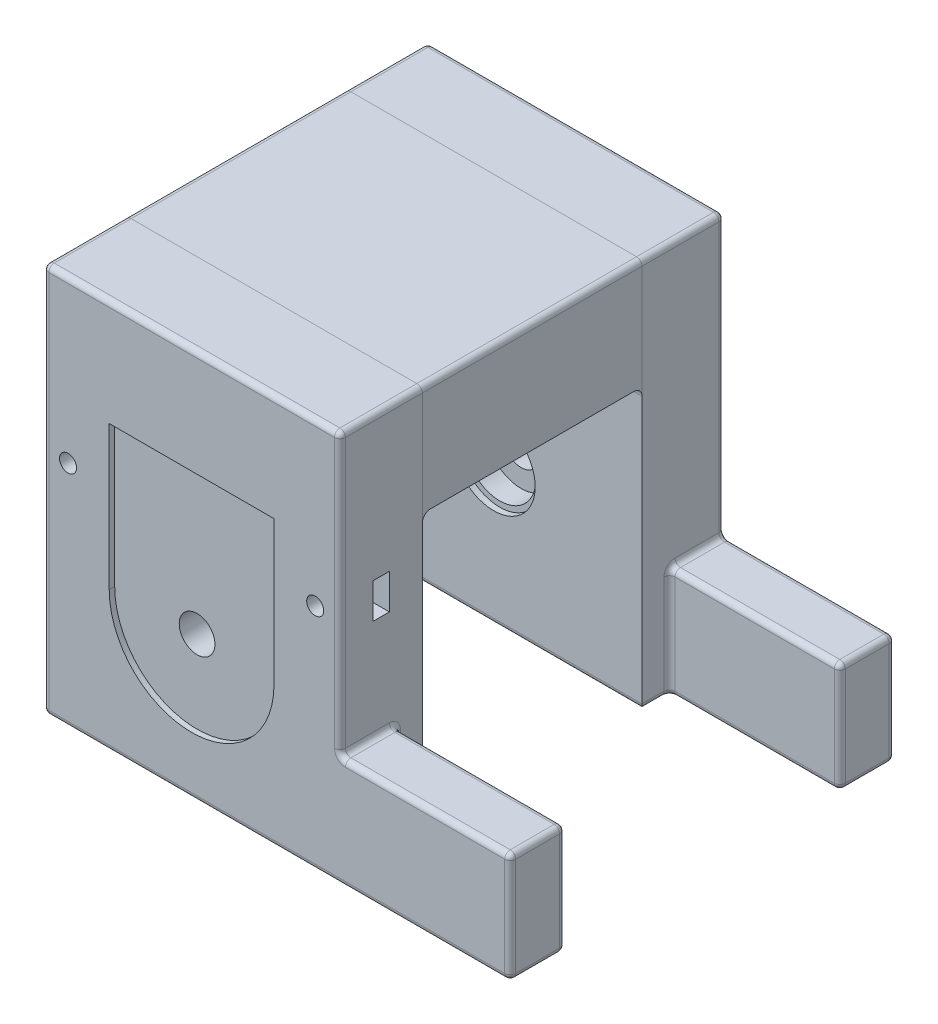
SolidWorks part; units mm, degrees
note: The reader was unsure of these and kept them because the rebuilt part matched: shared geometry of "Esquisse6<4>", "Esquisse6<5>".
ref_plane "Plan de face" through (0, 0, 0) normal (0, 0, 1) x (1, 0, 0)
ref_plane "Plan de dessus" through (0, 0, 0) normal (0, 1, 0) x (1, 0, 0)
ref_plane "Plan de droite" through (0, 0, 0) normal (1, 0, 0) x (0, 0, -1)
sketch "Esquisse1" plane through (0, 0, 0) normal (0, 0, 1) x (1, 0, 0)
  line L0 (0, 15.5) -> (0, -15.5)
  line L2 (0, -15.5) -> (31, -15.5)
  line L4 (0, 35.5) -> (-54, 35.5)
  line L5 (0, 0) -> (5.3833, 0) construction
  line L6 (31, -15.5) -> (31, -35.5)
  line L7 (31, -35.5) -> (-54, -35.5)
  line L8 (-54, 35.5) -> (-54, -35.5)
  line L9 (0, 15.5) -> (0, 35.5)
  point P4 (0, 0)
  dimension "D2" = 54
  dimension "D3" = 20
  dimension "D5" = 71
  dimension "D6" = 5.3833
  dimension "D1" = 31
extrude "Boss.-Extru.1" add sketch "Esquisse1" along normal blind 10
sketch "Esquisse2" plane through (0, 0, 10) normal (0, 0, 1) x (1, 0, 0)
  line L27 (0, 35.5) -> (0, -35.5)
  line L29 (-54, -35.5) -> (31, -35.5) construction
  line L30 (0, 35.5) -> (-54, 35.5)
  line L31 (-54, 35.5) -> (-54, -35.5)
  line L32 (-54, -35.5) -> (0, -35.5)
  point P3 (0, 0)
  point P12 (0, 0)
  point P17 (0, 0)
extrude "Boss.-Extru.2" add sketch "Esquisse2" along normal blind 50
ref_plane "Plan1" through (0, 0, 35) normal (0, 0, 1) x (1, 0, 0)
mirror "Symétrie2" about plane through (0, 0, 35) normal (0, 0, 1) of "Boss.-Extru.1"
fillet "Congé2" radius 1 30 edges at (15.5, -15.5, 0) (31, -15.5, 5) (31, -35.5, 5) (-54, -35.5, 35) (-54, 35.5, 35) (0, 35.5, 35) (0, -15.5, 5) (15.5, -35.5, 10) (0, -25.5, 10) (0, -35.5, 35) (0, -25.5, 60) (31, -25.5, 10) (15.5, -15.5, 60) (0, -15.5, 65) (31, -25.5, 60) (31, -15.5, 65) (15.5, -35.5, 60) (31, -35.5, 65) (15.5, -15.5, 70) (0, 10, 70) (-27, 35.5, 70) (-54, 0, 70) (-11.5, -35.5, 70) (31, -25.5, 70) (15.5, -15.5, 10) (31, -25.5, 0) (-11.5, -35.5, 0) (-54, 0, 0) (-27, 35.5, 0) (0, 10, 0)
sketch "Esquisse3" plane through (-54, 0, 0) normal (-1, 0, 0) x (0, 0, 1)
  line L0 (0, 0) -> (35, 0) construction
  line L1 (35, 0) -> (35, 15.5) construction
  line L6 (16.5, 15.5) -> (53.5, 15.5)
  line L7 (15, 14) -> (15, -35.5)
  line L8 (55, 14) -> (55, -35.5)
  line L9 (55, -35.5) -> (15, -35.5)
  line L11 (69, -35.5) -> (1, -35.5) construction
  arc A4 (53.5, 15.5) -> (55, 14) centre (53.5, 14) cw
  arc A5 (16.5, 15.5) -> (15, 14) centre (16.5, 14) ccw
  point P7 (35, 15.5)
  point P11 (55, 15.5)
  point P14 (15, 15.5)
  dimension "D4" = 1.5
  dimension "D1" = 35
  dimension "D2" = 15.5
  dimension "D3" = 40
extrude "Enlèv. mat.-Extru.1" cut sketch "Esquisse3" against normal through all
sketch "Esquisse6" plane through (0, 0, 15) normal (0, 0, 1) x (1, 0, 0)
  line L0 (-54, -10) -> (-27, -10)
  line L4 (0, 14) -> (0, -34.5) construction
  line L5 (-1, -35.5) -> (-53, -35.5) construction
  line L6 (-54, 14) -> (-54, -34.5) construction
  circle A0 centre (-27, -10) radius 7.55
  circle A1 centre (-27, -10) radius 6.55
  circle A2 centre (-27, -10) radius 3.25
  dimension "D3" = 15.1
  dimension "D4" = 13.1
  dimension "D5" = 6.5
  dimension "D1" = 27
  dimension "D2" = 25.5
extrude "Enlèv. mat.-Extru.3" cut sketch "Esquisse6" against normal blind 1.1 contours A0
extrude "Enlèv. mat.-Extru.4" cut sketch "Esquisse6<4>" against normal blind 5
sketch "Esquisse6<4>" plane through (0, 0, 15) normal (0, 0, 1) x (1, 0, 0) same geometry as "Esquisse6"
extrude "Enlèv. mat.-Extru.5" cut sketch "Esquisse6<5>" against normal through all
sketch "Esquisse6<5>" plane through (0, 0, 15) normal (0, 0, 1) x (1, 0, 0) same geometry as "Esquisse6"
mirror "Symétrie3" about plane through (0, 0, 35) normal (0, 0, 1) of "Enlèv. mat.-Extru.5", "Enlèv. mat.-Extru.4", "Enlèv. mat.-Extru.3"
sketch "Esquisse7" plane through (0, 0, 70) normal (0, 0, 1) x (1, 0, 0)
  line L8 (-42, -10) -> (-42, 16.2)
  line L9 (-12, -10) -> (-12, 16.2)
  line L10 (-12, 16.2) -> (-42, 16.2)
  circle A1 centre (-27, -10) radius 3.25 construction
  circle A2 centre (-27, -10) radius 3.25
  arc A3 (-42, -10) -> (-12, -10) centre (-27, -10) ccw
  dimension "D1" = 15
  dimension "D2" = 26.2
  dimension "D3" = 26.2
extrude "Enlèv. mat.-Extru.6" cut sketch "Esquisse7" against normal blind 1
sketch "Esquisse8" plane through (0, 0, 70) normal (0, 0, 1) x (1, 0, 0)
  line L0 (-12, 16.2) -> (-42, 16.2) construction
  line L1 (-12, -10) -> (-12, 16.2) construction
  line L2 (0, 6.2) -> (0, 35.5) construction
  line L3 (-27, 35.5) -> (0, 35.5) construction
  line L5 (-27, 35.5) -> (-27, 28.5) construction
  line L8 (-4.5, 6.2) -> (0, 6.2) construction
  line L9 (-54, -34.5) -> (-54, 34.5) construction
  line L10 (-53, 35.5) -> (-1, 35.5) construction
  circle A0 centre (-4.5, 6.2) radius 1.55
  circle A1 centre (-49.5, 6.2) radius 1.55
  dimension "D3" = 3.1
  dimension "D4" = 7
  dimension "D6" = 3.1
  dimension "D1" = 4.5
  dimension "D2" = 29.3
  dimension "D5" = 4.5
  dimension "D7" = 29.3
extrude "Enlèv. mat.-Extru.7" cut sketch "Esquisse8" against normal up to next
sketch "Esquisse10" plane through (0, 0, 70) normal (0, 0, 1) x (1, 0, 0)
  circle A1 centre (-4.5, 6.2) radius 3.2
  dimension "D2" = 6.4
sketch "Esquisse9" plane through (0, 0, 0) normal (1, 0, 0) x (0, 0, -1)
  line L0 (-35, 35.5) -> (-70, 35.5) construction
  line L1 (-69, 35.5) -> (-1, 35.5) construction
  line L2 (-70, 35.5) -> (-70, 6.2) construction
  line L4 (-70, 6.2) -> (-62.5, 6.2) construction
  line L12 (-70, -14.5) -> (-70, 34.5) construction
  line L13 (-64, 9.4) -> (-61, 9.4)
  line L14 (-64, 9.4) -> (-64, 3)
  line L15 (-64, 3) -> (-61, 3)
  line L16 (-61, 9.4) -> (-61, 3)
  line L17 (-64, 9.4) -> (-61, 3) construction
  line L18 (-64, 3) -> (-61, 9.4) construction
  dimension "D3" = 3
  dimension "D1" = 29.3
  dimension "D2" = 7.5
  dimension "D4" = 6.4
extrude "Enlèv. mat.-Extru.11" cut sketch "Esquisse10" against normal blind 3 from offset 6 offset against normal yes
extrude "Enlèv. mat.-Extru.12" cut sketch "Esquisse9" against normal blind 4.5
ref_plane "Plan2" through (-27, 0, 0) normal (1, 0, 0) x (0, 0, -1)
mirror "Symétrie4" about plane through (-27, 0, 0) normal (1, 0, 0) of "Enlèv. mat.-Extru.12", "Enlèv. mat.-Extru.11"
fillet "Congé3" radius 1 6 edges at (-0.2929, -35.2071, 15) (-0.2929, -35.2071, 55) (-53.7071, -35.2071, 55) (-27, -35.5, 55) (-53.7071, -35.2071, 15) (-27, -35.5, 15)
sketch "Esquisse11" plane through (-54, 0, 0) normal (-1, 0, 0) x (0, 0, 1)
  line L0 (15, -34.5) -> (15, 35.5)
  line L1 (1, 35.5) -> (69, 35.5) construction
  line L2 (55, -34.5) -> (55, 35.5)
  line L3 (55, 35.5) -> (15, 35.5)
  line L4 (14, -35.5) -> (15, -35.5) construction
  line L5 (15, -34.5) -> (15, -35.5)
  line L6 (15, -35.5) -> (55, -35.5)
  line L7 (55, -35.5) -> (55, -34.5)
  dimension "D1" = 40
split "Fractionner1" trim tools "Esquisse11" bodies to split 120 resulting bodies 121 122 123
equation "\"length\"= 54"
equation "\"D2@Esquisse1\"=\"length\""
equation "\"D1@Esquisse6\"=\"length\"/2"
